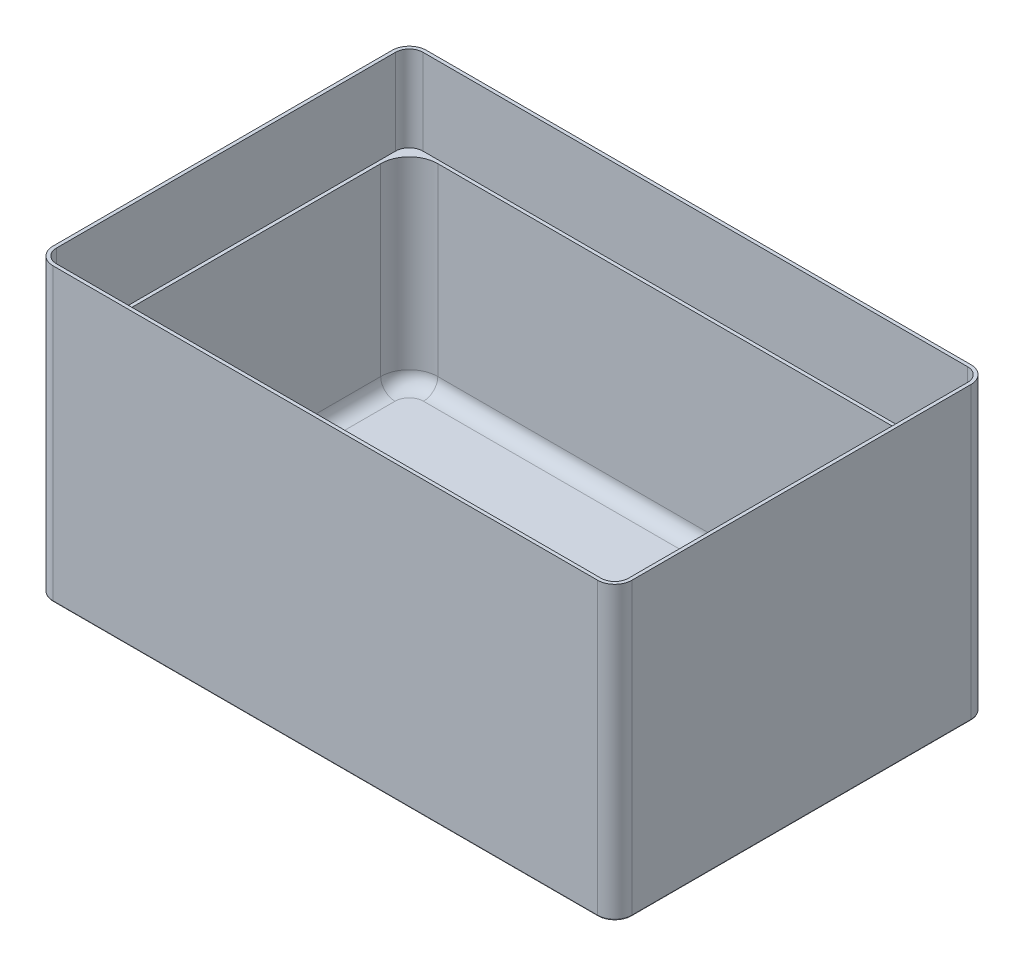
SolidWorks part; units mm, degrees
ref_plane "Front Plane" through (0, 0, 0) normal (0, 0, 1) x (1, 0, 0)
ref_plane "Top Plane" through (0, 0, 0) normal (0, 1, 0) x (1, 0, 0)
ref_plane "Right Plane" through (0, 0, 0) normal (1, 0, 0) x (0, 0, -1)
sketch "Sketch1" plane through (0, 0, 0) normal (0, 1, 0) x (1, 0, 0)
  line L0 (-2.4, 2.4) -> (-2.4, -128.4)
  line L1 (0, 0) -> (198, 0)
  line L2 (0, 0) -> (0, -126)
  line L3 (0, -126) -> (198, -126)
  line L4 (198, 0) -> (198, -126)
  line L5 (-2.4, -128.4) -> (200.4, -128.4)
  line L6 (200.4, 2.4) -> (200.4, -128.4)
  line L7 (-2.4, 2.4) -> (200.4, 2.4)
  dimension "D1" = 198
  dimension "D2" = 126
  dimension "D3" = 2.4
extrude "Boss-Extrude1" add sketch "Sketch1" along normal blind 102
sketch "Sketch3" plane through (0, 0, 0) normal (0, -1, 0) x (-1, 0, 0)
  line L1 (0, -126) -> (-198, -126)
  line L2 (0, -126) -> (0, 0)
  line L3 (0, 0) -> (-198, 0)
  line L4 (-198, -126) -> (-198, 0)
extrude "Boss-Extrude3" add sketch "Sketch3" against normal blind 2.4
fillet "Fillet1" radius 5 4 edges at (99, 2.4, 126) (99, 2.4, 0) (0, 2.4, 63) (198, 2.4, 63)
fillet "Fillet4" radius 10 8 edges at (1.4645, 3.8645, 1.4645) (196.5355, 3.8645, 1.4645) (196.5355, 3.8645, 124.5355) (1.4645, 3.8645, 124.5355) (0, 54.7, 126) (198, 54.7, 126) (198, 54.7, 0) (0, 54.7, 0)
fillet "Fillet2" radius 6 4 edges at (-2.4, 51, 128.4) (-2.4, 51, -2.4) (200.4, 51, -2.4) (200.4, 51, 128.4)
fillet "Fillet3" radius 0.4 8 edges at (198.6426, 0, 126.6426) (200.4, 0, 63) (198.6426, 0, -0.6426) (99, 0, -2.4) (-0.6426, 0, -0.6426) (-2.4, 0, 63) (-0.6426, 0, 126.6426) (99, 0, 128.4)
sketch "Sketch7" plane through (0, 102, 0) normal (0, 1, 0) x (1, 0, 0)
  line L24 (3.6, -127.2) -> (194.4, -127.2)
  line L25 (199.2, -122.4) -> (199.2, -3.6)
  line L26 (194.4, 1.2) -> (3.6, 1.2)
  line L27 (-1.2, -3.6) -> (-1.2, -122.4)
  line L28 (3.6, -127.2) -> (194.4, -127.2)
  line L29 (199.2, -122.4) -> (199.2, -3.6)
  line L30 (194.4, 1.2) -> (3.6, 1.2)
  line L31 (-1.2, -3.6) -> (-1.2, -122.4)
  arc A20 (-1.2, -122.4) -> (3.6, -127.2) centre (3.6, -122.4) ccw
  arc A21 (194.4, -127.2) -> (199.2, -122.4) centre (194.4, -122.4) ccw
  arc A22 (199.2, -3.6) -> (194.4, 1.2) centre (194.4, -3.6) ccw
  arc A23 (3.6, 1.2) -> (-1.2, -3.6) centre (3.6, -3.6) ccw
  arc A24 (-1.2, -122.4) -> (3.6, -127.2) centre (3.6, -122.4) ccw
  arc A25 (194.4, -127.2) -> (199.2, -122.4) centre (194.4, -122.4) ccw
  arc A26 (199.2, -3.6) -> (194.4, 1.2) centre (194.4, -3.6) ccw
  arc A27 (3.6, 1.2) -> (-1.2, -3.6) centre (3.6, -3.6) ccw
  dimension "D1" = 1.2
extrude "Cut-Extrude1" cut sketch "Sketch7" against normal blind 30
equation "\"D1@Boss-Extrude1\"=85*1.2"
equation "\"D1@Sketch1\"=165 * 1.2"
equation "\"D2@Sketch1\"=105*1.2"
